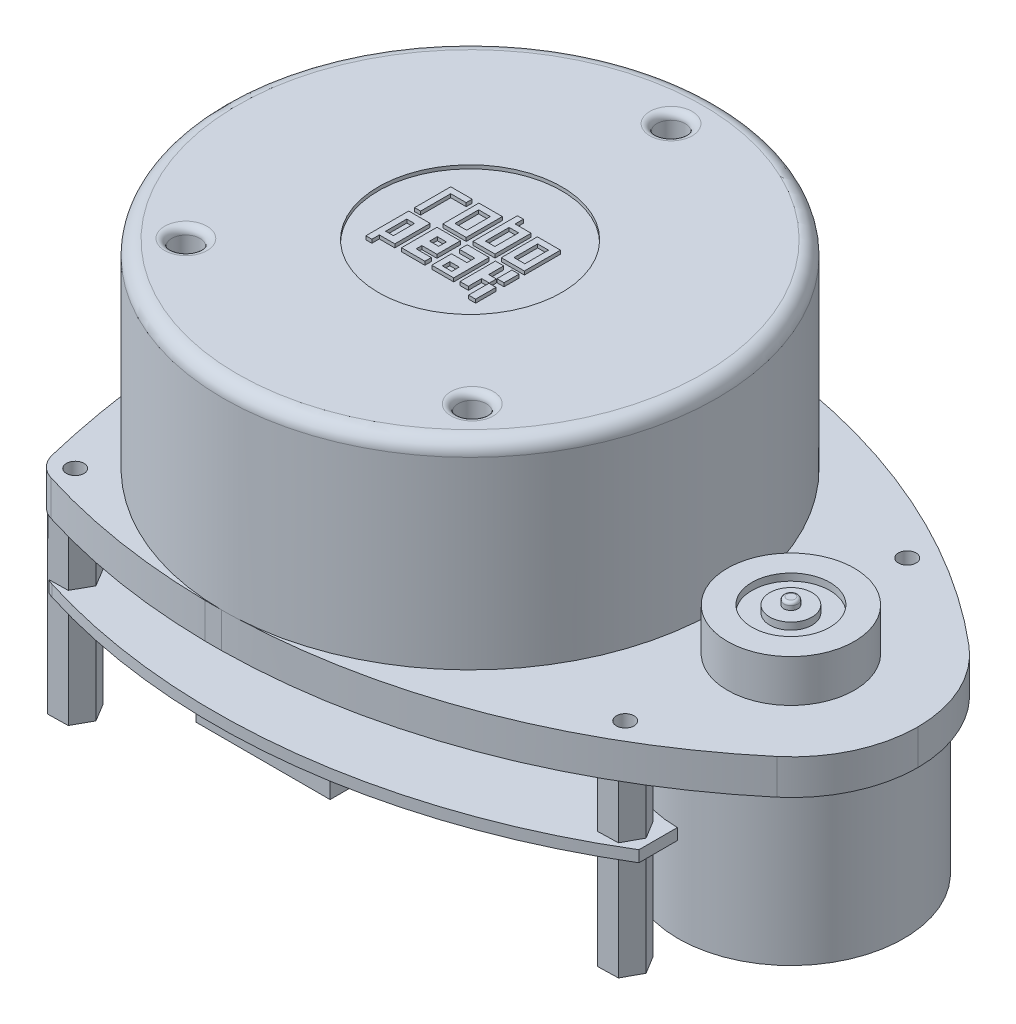
SolidWorks part; units mm, degrees
ref_plane "Спереди" through (0, 0, 0) normal (0, 0, 1) x (1, 0, 0)
ref_plane "Сверху" through (0, 0, 0) normal (0, 1, 0) x (1, 0, 0)
ref_plane "Справа" through (0, 0, 0) normal (1, 0, 0) x (0, 0, -1)
sketch "Эскиз1" plane through (0, 0, 0) normal (0, 1, 0) x (1, 0, 0)
  line L1 (-49.25, 35) -> (49.25, 35)
  line L2 (-49.25, 35) -> (-49.25, -35)
  line L3 (-49.25, -35) -> (49.25, -35)
  line L4 (49.25, 35) -> (49.25, -35)
  line L5 (-49.25, 35) -> (49.25, -35) construction
  line L6 (-49.25, -35) -> (49.25, 35) construction
  point P0 (0, 0)
  dimension "D1" = 98.5
  dimension "D2" = 70
extrude "Бобышка-Вытянуть1" add sketch "Эскиз1" along normal blind 5
sketch "Эскиз2" plane through (0, 5, 0) normal (0, 1, 0) x (1, 0, 0)
  line L0 (-49.25, 35) -> (-49.25, -35) construction
  circle A0 centre (-14.25, 0) radius 35
  point P2 (-49.25, 0)
  point P3 (-49.25, 0)
extrude "Бобышка-Вытянуть2" add sketch "Эскиз2" along normal blind 28.1
sketch "Эскиз3" plane through (0, 33.1, 0) normal (0, 1, 0) x (1, 0, 0)
  line L0 (-14.25, 0) -> (-14.25, 50000) construction
  line L1 (-14.25, -20) -> (-26.2883, -20) construction
  line L2 (-49.25, -35) -> (-14.25, -35) construction
  circle A0 centre (-14.25, 28.5) radius 2
  circle A1 centre (-34.5539, -20) radius 2
  circle A2 centre (6.0539, -20) radius 2
  arc A3 (-49.25, 0) -> (-14.25, -35) centre (-14.25, 0) ccw construction
  circle A4 centre (-14.25, 0) radius 35 construction
  dimension "D2" = 4
  dimension "D1" = 6.5
  dimension "D3" = 15
  dimension "D4" = 28.5
  dimension "D5" = 28.5
extrude "Вырез-Вытянуть1" cut sketch "Эскиз3" against normal blind 5
fillet "Скругление1" radius 2 1 edges at (-14.25, 33.1, 35)
fillet "Скругление2" radius 1 3 edges at (6.0539, 33.1, 22) (-34.5539, 33.1, 22) (-14.25, 33.1, -26.5)
sketch "Эскиз4" plane through (0, 33.1, 0) normal (0, 1, 0) x (1, 0, 0)
  line L0 (-22.1152, -6.9149) -> (-22.1152, -0.8316)
  line L1 (-22.1152, -0.8316) -> (-19.0735, -0.8316)
  line L2 (-19.0735, -0.8316) -> (-19.0735, -5.8538)
  line L3 (-19.0735, -5.8538) -> (-21.2663, -5.8538)
  line L4 (-21.2663, -5.8538) -> (-21.2663, -6.9149)
  line L5 (-21.2663, -6.9149) -> (-22.1152, -6.9149)
  line L6 (-22.1152, 0) -> (-22.1152, 5.1201)
  line L7 (-22.1152, 5.1201) -> (-19.0735, 5.1201)
  line L8 (-19.0735, 5.1201) -> (-19.0735, 4.2707)
  line L9 (-19.0735, 4.2707) -> (-21.2663, 4.2707)
  line L10 (-21.2663, 4.2707) -> (-21.2663, 0)
  line L11 (-21.2663, 0) -> (-22.1152, 0)
  line L12 (-21.2663, -1.9579) -> (-20.1699, -1.9579)
  line L13 (-20.1699, -1.9579) -> (-20.1699, -4.9509)
  line L14 (-20.1699, -4.9509) -> (-21.2663, -4.9509)
  line L15 (-21.2663, -4.9509) -> (-21.2663, -1.9579)
  line L16 (-13.8296, 0) -> (-13.8296, 6.293)
  line L17 (-18.1168, 0) -> (-14.8003, 0)
  line L18 (-18.1168, 0) -> (-18.1168, 5.1201)
  line L19 (-18.1168, 5.1201) -> (-14.8003, 5.1201)
  line L20 (-14.8003, 0) -> (-14.8003, 5.1201)
  line L21 (-9.8255, 5.1201) -> (-6.5494, 5.1201)
  line L22 (-9.8255, 5.1201) -> (-9.8255, 0)
  line L23 (-9.8255, 0) -> (-6.5494, 0)
  line L24 (-6.5494, 5.1201) -> (-6.5494, 0)
  line L25 (-8.9357, 4.2707) -> (-7.3988, 4.2707)
  line L26 (-8.9357, 4.2707) -> (-8.9357, 0.9137)
  line L27 (-8.9357, 0.9137) -> (-7.3988, 0.9137)
  line L28 (-7.3988, 4.2707) -> (-7.3988, 0.9137)
  line L29 (-17.3079, 4.2707) -> (-15.6497, 4.2707)
  line L30 (-17.3079, 4.2707) -> (-17.3079, 0.9137)
  line L31 (-17.3079, 0.9137) -> (-15.6497, 0.9137)
  line L32 (-15.6497, 4.2707) -> (-15.6497, 0.9137)
  line L33 (-12.9802, 4.2707) -> (-11.6455, 4.2707)
  line L34 (-12.9802, 4.2707) -> (-12.9802, 0.9137)
  line L35 (-12.9802, 0.9137) -> (-11.6455, 0.9137)
  line L36 (-11.6455, 4.2707) -> (-11.6455, 0.9137)
  line L37 (-12.9802, -4.142) -> (-11.6455, -4.142)
  line L38 (-12.9802, -4.142) -> (-12.9802, -5.1936)
  line L39 (-12.9802, -5.1936) -> (-11.6455, -5.1936)
  line L40 (-11.6455, -4.142) -> (-11.6455, -5.1936)
  line L41 (-16.9439, -1.9579) -> (-15.6497, -1.9579)
  line L42 (-16.9439, -1.9579) -> (-16.9439, -3.0499)
  line L43 (-16.9439, -3.0499) -> (-15.6497, -3.0499)
  line L44 (-15.6497, -1.9579) -> (-15.6497, -3.0499)
  line L46 (-7.5508, -0.7643) -> (-6.5494, -0.7643)
  line L47 (-7.5508, -0.7643) -> (-7.5508, -2.8858)
  line L48 (-7.5508, -2.8858) -> (-6.5494, -2.8858)
  line L49 (-6.5494, -0.7643) -> (-6.5494, -2.8858)
  line L50 (-6.5494, -6.9149) -> (-7.5508, -6.9149)
  line L51 (-6.5494, -6.9149) -> (-6.5494, -4.0216)
  line L52 (-6.5494, -4.0216) -> (-7.5508, -4.0216)
  line L53 (-13.8296, 6.293) -> (-12.9802, 6.293)
  line L54 (-12.9802, 6.293) -> (-12.9802, 5.1201)
  line L55 (-12.9802, 5.1201) -> (-10.7153, 5.1201)
  line L56 (-10.7153, 5.1201) -> (-10.7153, 0)
  line L57 (-10.7153, 0) -> (-13.8296, 0)
  line L58 (-9.8255, -0.8316) -> (-8.6437, -0.8316)
  line L59 (-8.6437, -0.8316) -> (-8.6437, -2.9608)
  line L60 (-8.6437, -2.9608) -> (-7.5508, -2.9608)
  line L61 (-9.8255, -0.8316) -> (-9.8255, -5.8538)
  line L62 (-9.8255, -5.8538) -> (-8.6437, -5.8538)
  line L63 (-8.6437, -5.8538) -> (-8.6437, -3.9573)
  line L64 (-8.6437, -3.9573) -> (-7.5508, -3.9573)
  line L65 (-7.5508, -2.9608) -> (-7.5508, -3.9573)
  line L66 (-13.8296, -0.8316) -> (-10.7153, -0.8316)
  line L67 (-10.7153, -0.8316) -> (-10.7153, -5.8538)
  line L68 (-10.7153, -5.8538) -> (-13.8296, -5.8538)
  line L69 (-13.8296, -5.8538) -> (-13.8296, -3.0499)
  line L70 (-13.8296, -3.0499) -> (-11.6455, -3.0499)
  line L71 (-11.6455, -3.0499) -> (-11.6455, -1.9408)
  line L72 (-11.6455, -1.9408) -> (-13.8296, -1.9408)
  line L73 (-13.8296, -1.9408) -> (-13.8296, -0.8316)
  line L74 (-18.1168, -0.8316) -> (-14.8003, -0.8316)
  line L75 (-14.8003, -0.8316) -> (-14.8003, -4.142)
  line L76 (-14.8003, -4.142) -> (-16.9439, -4.142)
  line L77 (-16.9439, -4.142) -> (-16.9439, -4.9509)
  line L78 (-16.9439, -4.9509) -> (-14.8003, -4.9509)
  line L79 (-14.8003, -4.9509) -> (-14.8003, -5.8538)
  line L80 (-14.8003, -5.8538) -> (-18.1168, -5.8538)
  line L81 (-18.1168, -5.8538) -> (-18.1168, -0.8316)
  line L82 (-7.5508, -6.9149) -> (-7.5508, -4.0216)
  circle A0 centre (-14.25, 0) radius 13
  dimension "D1" = 26
extrude "Вырез-Вытянуть3" cut sketch "Эскиз4" against normal blind 0.5 contours A0 L50 L82 L52 L51 L72 L73 L66 L67 L68 L69 L70 L71 L56 L57 L16 L53 L54 L55 L10 L11 L6 L7 L8 L9 L4 L5 L0 L1 L2 L3 L20 L17 L18 L19 L21 L24 L23 L22 L46 L49 L48 L47 | L32 L29 L30 L31 | L36 L33 L34 L35 | L28 L25 L26 L27 | L44 L41 L42 L43 | L15 L14 L13 L12 | L37 L40 L39 L38 region at (-20.7181, 33.1, 3.4544) region at (-8.1672, 33.1, -2.5922) region at (-16.4788, 33.1, -2.5922) region at (-12.3129, 33.1, -2.5922) region at (-16.2968, 33.1, 2.5039) region at (-14.2871, 33.1, -0.0991)
sketch "Эскиз5" plane through (0, 5, 0) normal (0, 1, 0) x (1, 0, 0)
  line L0 (-42.25, 30.7255) -> (-42.25, -39.5827) construction
  line L1 (27.75, 26.9972) -> (27.75, -49973.0028) construction
  line L2 (-49.25, 0) -> (49950.75, 0) construction
  circle A0 centre (-14.25, 0) radius 33 construction
  circle A1 centre (-42.25, 28) radius 1.25
  circle A2 centre (27.75, 20) radius 1.25
  circle A3 centre (27.75, -20) radius 1.25
  circle A4 centre (-42.25, -28) radius 1.25
  point P4 (-14.25, 33)
  dimension "D1" = 28
  dimension "D3" = 2.5
  dimension "D2" = 42
  dimension "D4" = 28
  dimension "D5" = 20
extrude "Вырез-Вытянуть4" cut sketch "Эскиз5" against normal blind 5
sketch "Эскиз6" plane through (0, 5, 0) normal (0, 1, 0) x (1, 0, 0)
  line L0 (49.25, 0) -> (50049.25, 0) construction
  line L1 (49.25, -35) -> (49.25, 35) construction
  circle A0 centre (31.25, 0) radius 9
  arc A1 (-14.25, -35) -> (-14.25, 35) centre (-14.25, 0) ccw construction
  point P4 (49.25, 0)
  dimension "D1" = 18
  dimension "D2" = 45.5
extrude "Бобышка-Вытянуть3" add sketch "Эскиз6" along normal blind 7
sketch "Эскиз7" plane through (0, 12, 0) normal (0, 1, 0) x (1, 0, 0)
  circle A0 centre (31.25, 0) radius 9
  circle A1 centre (31.25, 0) radius 0.9935
extrude "Вырез-Вытянуть5" cut sketch "Эскиз7" against normal blind 1
sketch "Эскиз8" plane through (0, 11, 0) normal (0, 1, 0) x (1, 0, 0)
  circle A0 centre (31.25, 0) radius 3.0011
  circle A1 centre (31.25, 0) radius 5.5217
extrude "Вырез-Вытянуть6" cut sketch "Эскиз8" against normal blind 1
fillet "Скругление3" radius 0.4 1 edges at (31.25, 12, 0.9935)
sketch "Эскиз9" plane through (0, 5, 0) normal (0, 1, 0) x (1, 0, 0)
  circle A0 centre (31.25, 0) radius 16
  dimension "D1" = 32
extrude "Бобышка-Вытянуть4" add sketch "Эскиз9" against normal blind 27
sketch "Эскиз10" plane through (0, 0, 0) normal (0, -1, 0) x (1, 0, 0)
  line L0 (-49.25, 0) -> (49950.75, 0) construction
  line L1 (-40.8546, 25.4729) -> (-39.3638, 27.9449)
  line L2 (-39.3638, 27.9449) -> (-40.7592, 30.472)
  line L3 (-40.7592, 30.472) -> (-43.6454, 30.5271)
  line L4 (-43.6454, 30.5271) -> (-45.1362, 28.0551)
  line L5 (-45.1362, 28.0551) -> (-43.7408, 25.528)
  line L6 (-43.7408, 25.528) -> (-40.8546, 25.4729)
  line L7 (29.2571, 22.4621) -> (26.3713, 22.5363)
  line L8 (26.3713, 22.5363) -> (24.8642, 20.0742)
  line L9 (24.8642, 20.0742) -> (26.2429, 17.5379)
  line L10 (26.2429, 17.5379) -> (29.1287, 17.4637)
  line L11 (29.1287, 17.4637) -> (30.6358, 19.9258)
  line L12 (30.6358, 19.9258) -> (29.2571, 22.4621)
  line L13 (30.6358, -19.9258) -> (29.2571, -22.4621)
  line L14 (29.1287, -17.4637) -> (30.6358, -19.9258)
  line L15 (26.2429, -17.5379) -> (29.1287, -17.4637)
  line L16 (24.8642, -20.0742) -> (26.2429, -17.5379)
  line L17 (26.3713, -22.5363) -> (24.8642, -20.0742)
  line L18 (29.2571, -22.4621) -> (26.3713, -22.5363)
  line L19 (-43.7408, -25.528) -> (-40.8546, -25.4729)
  line L20 (-45.1362, -28.0551) -> (-43.7408, -25.528)
  line L21 (-43.6454, -30.5271) -> (-45.1362, -28.0551)
  line L22 (-40.7592, -30.472) -> (-43.6454, -30.5271)
  line L23 (-39.3638, -27.9449) -> (-40.7592, -30.472)
  line L24 (-40.8546, -25.4729) -> (-39.3638, -27.9449)
  circle A0 centre (-42.25, 28) radius 2.5 construction
  circle A1 centre (27.75, 20) radius 2.5 construction
  circle A2 centre (27.75, -20) radius 2.5 construction
  circle A3 centre (-42.25, -28) radius 2.5 construction
  point P17 (27.75, 20)
  dimension "D1" = 5
  dimension "D2" = 5
extrude "Бобышка-Вытянуть5" add sketch "Эскиз10" along normal blind 24.6
sketch "Эскиз11" plane through (0, 5, 0) normal (0, 1, 0) x (1, 0, 0)
  circle A0 centre (-14.25, 0) radius 26
  dimension "D1" = 52
extrude "Бобышка-Вытянуть6" add sketch "Эскиз11" against normal blind 8
fillet "Скругление4" radius 1 1 edges at (-14.25, -3, 26)
sketch "Эскиз12" plane through (0, 5, 0) normal (0, 1, 0) x (1, 0, 0)
  line L1 (49.25, -35) -> (49.25, 35) construction
  line L2 (-49.25, 0) -> (-50049.25, 0) construction
  line L4 (-54.0511, 37.7308) -> (52.2004, 37.7308)
  line L5 (-54.0511, 37.7308) -> (-54.0511, -37.8351)
  line L6 (-54.0511, -37.8351) -> (52.2004, -37.8351)
  line L7 (52.2004, 37.7308) -> (52.2004, -37.8351)
  arc A0 (-49.25, 0) -> (-45.5286, 27.9743) centre (86.6751, -3.8473) cw
  circle A1 centre (-14.25, 0) radius 35 construction
  arc A3 (49.25, 0) -> (42.909, 13.5993) centre (31.4018, -0.0442) ccw
  arc A4 (-49.25, 0) -> (-14.25, -35) centre (-14.25, 0) ccw construction
  arc A5 (-42.835, 30.8555) -> (42.909, 13.5993) centre (-15.6796, -55.8665) cw
  arc A6 (-45.5286, 27.9743) -> (-42.835, 30.8555) centre (-41.6397, 27.0383) cw
  arc A7 (-45.5286, -27.9743) -> (-42.835, -30.8555) centre (-41.6397, -27.0383) ccw
  arc A8 (-42.835, -30.8555) -> (42.909, -13.5993) centre (-15.6796, 55.8665) ccw
  arc A9 (49.25, 0) -> (42.909, -13.5993) centre (31.4018, 0.0442) cw
  arc A10 (-49.25, 0) -> (-45.5286, -27.9743) centre (86.6751, 3.8473) ccw
  dimension "D1" = 4
extrude "Вырез-Вытянуть7" cut sketch "Эскиз12" against normal blind 8
fillet "Скругление5" radius 100 1 edges at (-49.25, 2.5, 0)
sketch "Эскиз13" plane through (0, 0, 0) normal (0, -1, 0) x (1, 0, 0)
  line L0 (31.5536, 21.8603) -> (31.5536, 16.4)
  line L1 (31.5536, -16.4) -> (31.5536, -21.8603)
  arc A0 (-49.0982, 0) -> (-45.3768, 27.9743) centre (86.8269, -3.8473) cw
  arc A1 (31.5536, 16.4) -> (31.5536, -16.4) centre (31.5536, 0) ccw
  arc A2 (-42.6831, 30.8555) -> (31.5536, 21.8603) centre (-15.5278, -55.8665) cw
  arc A3 (-45.3768, 27.9743) -> (-42.6831, 30.8555) centre (-41.4878, 27.0383) cw
  arc A4 (-45.3768, -27.9743) -> (-42.6831, -30.8555) centre (-41.4878, -27.0383) ccw
  arc A5 (-42.6831, -30.8555) -> (31.5536, -21.8603) centre (-15.5278, 55.8665) ccw
  arc A7 (-49.0982, 0) -> (-45.3768, -27.9743) centre (86.8269, 3.8473) ccw
  arc A8 (-48.5248, 10.6929) -> (-48.5248, -10.6929) centre (50.9018, 0) ccw construction
  point P16 (-49.0982, 0)
  point P21 (-49.0982, 0)
  dimension "D1" = 4
  dimension "D2" = 32.8
extrude "Бобышка-Вытянуть7" add sketch "Эскиз13" along normal blind 1.6 from offset 8
sketch "Эскиз14" plane through (0, -9.6, 0) normal (0, -1, 0) x (1, 0, 0)
  line L1 (-24.0982, 30) -> (-4.0982, 30)
  line L2 (-24.0982, 30) -> (-24.0982, 25)
  line L3 (-24.0982, 25) -> (-4.0982, 25)
  line L4 (-4.0982, 30) -> (-4.0982, 25)
  circle A0 centre (-14.25, 0) radius 35 construction
  point P4 (-14.0982, 30)
  dimension "D1" = 5
  dimension "D2" = 20
  dimension "D3" = 35
  dimension "D4" = 30
extrude "Бобышка-Вытянуть8" add sketch "Эскиз14" along normal blind 6
chamfer "Фаска1" distance 1 angle 45 1 edges at (-24.0982, -12.6, 30)
sketch "Sketch1" plane through (0, 33.1, 0) normal (0, 1, 0) x (1, 0, 0)
  line L0 (18.75, 0) -> (-47.25, 0) construction
  line L1 (-14.25, -33) -> (-14.25, 33) construction
  circle A0 centre (-14.25, 0) radius 33 construction
